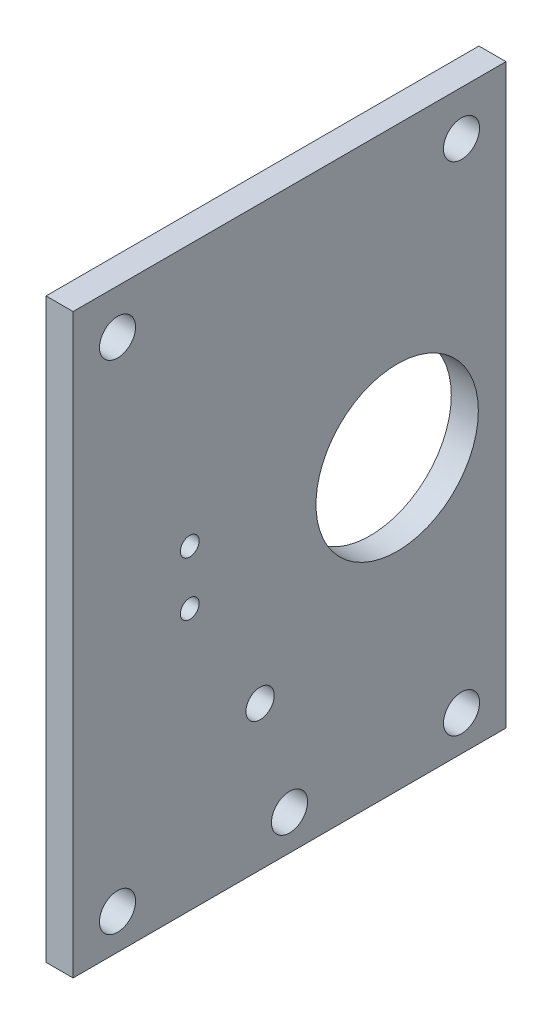
SolidWorks part; units mm, degrees
material "6061 Alloy"
ref_plane "Front Plane" through (0, 0, 0) normal (0, 0, 1) x (1, 0, 0)
ref_plane "Top Plane" through (0, 0, 0) normal (0, 1, 0) x (1, 0, 0)
ref_plane "Right Plane" through (0, 0, 0) normal (1, 0, 0) x (0, 0, -1)
sketch "Sketch2" plane through (0, 0, 0) normal (1, 0, 0) x (0, 0, -1)
  line L1 (-38.1, -50.8) -> (38.1, -50.8)
  line L2 (-38.1, -50.8) -> (-38.1, 50.8)
  line L3 (-38.1, 50.8) -> (38.1, 50.8)
  line L4 (38.1, -50.8) -> (38.1, 50.8)
  line L5 (-38.1, -50.8) -> (38.1, 50.8) construction
  line L6 (-38.1, 50.8) -> (38.1, -50.8) construction
  point P0 (0, 0)
  dimension "D1" = 76.2
  dimension "D2" = 101.6
extrude "Boss-Extrude1" add sketch "Sketch2" along normal blind 4.7625
sketch "Sketch3" plane through (4.7625, 0, 0) normal (1, 0, 0) x (0, 0, -1)
  line L5 (30.2768, -44.5643) -> (-30.2768, -44.5643) construction
  line L6 (-30.2768, 42.9768) -> (30.2768, 42.9768) construction
  line L7 (30.2768, 42.9768) -> (30.2768, -44.5643) construction
  line L8 (-30.2768, 42.9768) -> (-30.2768, -44.5643) construction
  line L9 (-38.1, 50.8) -> (-38.1, -50.8) construction
  line L10 (38.1, 50.8) -> (-38.1, 50.8) construction
  line L11 (38.1, -50.8) -> (38.1, 50.8) construction
  line L12 (-38.1, -50.8) -> (38.1, -50.8) construction
  circle A0 centre (30.2768, -44.5643) radius 3.175
  circle A1 centre (30.2768, 42.9768) radius 3.175
  circle A2 centre (-30.2768, 42.9768) radius 3.175
  circle A3 centre (-30.2768, -44.5643) radius 3.175
  circle A4 centre (18.9484, 0) radius 14.2875
  circle A5 centre (-5.1816, -25.4) radius 2.4892
  circle A6 centre (0, -44.5643) radius 3.175
  dimension "D1" = 6.35
  dimension "D5" = 7.8232
  dimension "D7" = 7.8232
  dimension "D8" = 6.2357
  dimension "D9" = 28.575
  dimension "D10" = 50.8
  dimension "D11" = 4.9784
  dimension "D12" = 25.4
  dimension "D6" = 7.8232
  dimension "D13" = 24.13
  dimension "D14" = 19.1516
extrude "Cut-Extrude1" cut sketch "Sketch3" against normal blind 6.35 contours A1
extrude "Cut-Extrude2" cut sketch "Sketch3<4>" against normal blind 6.35
sketch "Sketch3<4>" plane through (4.7625, 0, 0) normal (1, 0, 0) x (0, 0, -1) same geometry as "Sketch3"
hole_wizard "M6 Clearance Hole1" positions "Sketch5" profile "Sketch4" tap size "M4x0.7" standard "ANSI Metric" end condition up to next
sketch "Sketch5" plane through (4.7625, 0, 0) normal (1, 0, 0) x (0, 0, -1)
  circle A0 centre (-17.5641, 4.7625) radius 1.65 construction
  circle A1 centre (-17.5641, -4.7625) radius 1.65 construction
  point P0 (-17.5641, -4.7625)
  point P2 (-17.5641, 4.7625)
sketch "Sketch4" plane through (4.7625, -4.7625, 17.5641) normal (0, 1, 0) x (0, 0, -1)
  line L0 (0, 0) -> (0, 4.7625)
  line L1 (0, 4.7625) -> (1.65, 4.7625)
  line L2 (1.65, 4.7625) -> (1.65, 0)
  line L5 (1.65, 0) -> (0, 0)
  line L11 (0, -6.35) -> (0, 107.95) construction
  dimension "Thread Major Dia." = 3.3
  dimension "Thru Tap Drill Depth" = 4.7625
